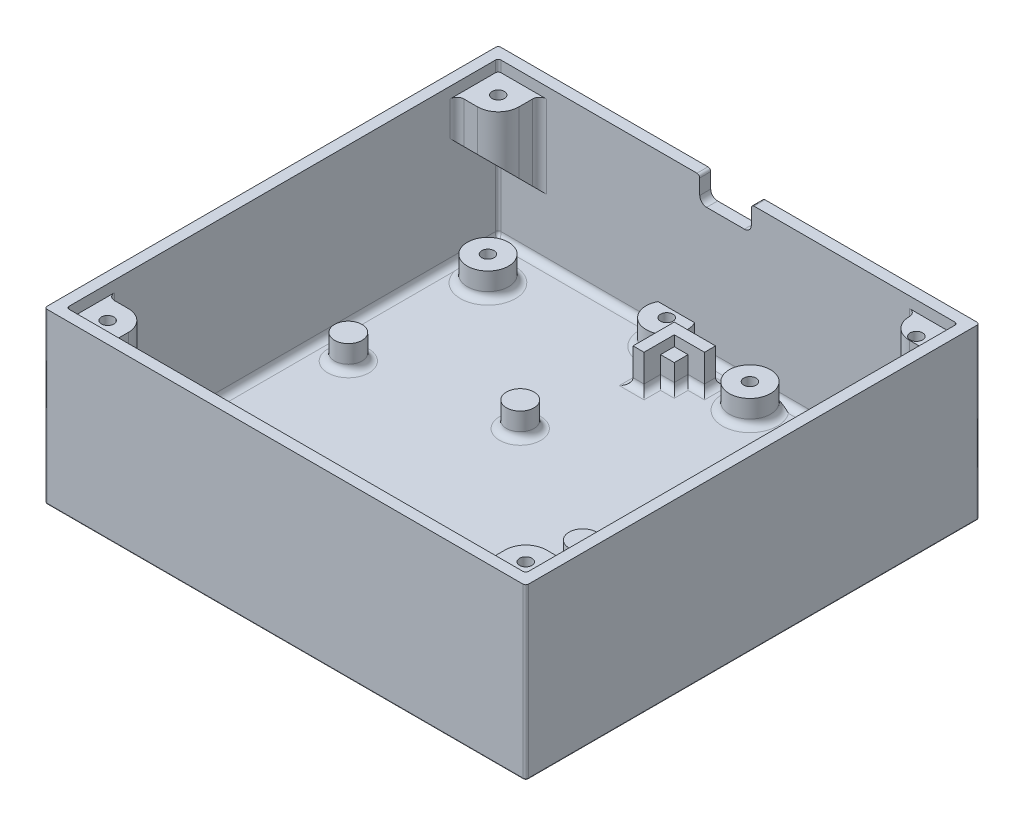
SolidWorks part; units mm, degrees
ref_plane "前视基准面" through (0, 0, 0) normal (0, 0, 1) x (1, 0, 0)
ref_plane "上视基准面" through (0, 0, 0) normal (0, 1, 0) x (1, 0, 0)
ref_plane "右视基准面" through (0, 0, 0) normal (1, 0, 0) x (0, 0, -1)
other "Configuration Table"
sketch "草图1" plane through (0, 0, 0) normal (0, 1, 0) x (1, 0, 0)
  line L1 (0, 0) -> (70, 0)
  line L2 (0, 0) -> (0, 66)
  line L3 (0, 66) -> (70, 66)
  line L4 (70, 0) -> (70, 66)
  dimension "D1" = 70
  dimension "D2" = 66
extrude "凸台-拉伸1" add sketch "草图1" along normal blind 2
sketch "草图2" plane through (0, 2, 0) normal (0, 1, 0) x (1, 0, 0)
  line L0 (70, 0) -> (70, 66) construction
  line L1 (66.8, 60) -> (31.6, 60)
  line L2 (66.8, 60) -> (66.8, 6)
  line L3 (66.8, 6) -> (31.6, 6)
  line L4 (31.6, 60) -> (31.6, 6)
  line L5 (70, 66) -> (0, 66) construction
  line L11 (68.4, 61.6) -> (30, 61.6)
  line L12 (30, 61.6) -> (30, 4.4)
  line L13 (68.4, 4.4) -> (30, 4.4)
  line L14 (68.4, 61.6) -> (68.4, 4.4)
  dimension "D1" = 35.2
  dimension "D2" = 54
  dimension "D3" = 3.2
  dimension "D4" = 6
  dimension "D5" = 1.6
extrude "凸台-拉伸2" add sketch "草图2" along normal blind 5
sketch "草图3" plane through (0, 2, 0) normal (0, 1, 0) x (1, 0, 0)
  line L0 (31.6, 6) -> (66.8, 6) construction
  line L1 (31.6, 60) -> (33.6, 60)
  line L2 (31.6, 60) -> (31.6, 58)
  line L3 (31.6, 58) -> (33.6, 58)
  line L4 (33.6, 60) -> (33.6, 58)
  line L5 (66.8, 60) -> (64.8, 60)
  line L6 (66.8, 60) -> (66.8, 58)
  line L7 (66.8, 58) -> (64.8, 58)
  line L8 (64.8, 60) -> (64.8, 58)
  line L9 (31.6, 6) -> (33.6, 6)
  line L10 (31.6, 6) -> (31.6, 8)
  line L11 (31.6, 8) -> (33.6, 8)
  line L12 (33.6, 6) -> (33.6, 8)
  line L13 (66.8, 6) -> (64.8, 6)
  line L14 (66.8, 6) -> (66.8, 8)
  line L15 (66.8, 8) -> (64.8, 8)
  line L16 (64.8, 6) -> (64.8, 8)
  line L17 (66.8, 6) -> (66.8, 60) construction
  circle A0 centre (49.3, 29) radius 2
  dimension "D9" = 4
  dimension "D11" = 17.5
  dimension "D1" = 2
  dimension "D2" = 2
  dimension "D3" = 2
  dimension "D4" = 2
  dimension "D5" = 2
  dimension "D6" = 2
  dimension "D7" = 2
  dimension "D8" = 2
  dimension "D10" = 23
extrude "凸台-拉伸3" add sketch "草图3" along normal blind 3.5
sketch "草图4" plane through (0, 7, 0) normal (0, 1, 0) x (1, 0, 0)
  line L0 (68.4, 61.6) -> (30, 61.6) construction
  line L1 (36, 61.6) -> (62.4, 61.6)
  line L2 (36, 61.6) -> (36, 60)
  line L3 (36, 60) -> (62.4, 60)
  line L4 (62.4, 61.6) -> (62.4, 60)
  line L5 (64.8, 60) -> (33.6, 60) construction
  line L6 (30, 61.6) -> (30, 4.4) construction
  line L7 (30, 55.6) -> (31.6, 55.6)
  line L8 (30, 55.6) -> (30, 10.4)
  line L9 (30, 10.4) -> (31.6, 10.4)
  line L10 (31.6, 55.6) -> (31.6, 10.4)
  line L11 (31.6, 58) -> (31.6, 8) construction
  line L12 (31.6, 6) -> (66.8, 6) construction
  line L13 (36, 6) -> (62.4, 6)
  line L14 (36, 6) -> (36, 4.4)
  line L15 (36, 4.4) -> (62.4, 4.4)
  line L16 (62.4, 6) -> (62.4, 4.4)
  line L17 (30, 4.4) -> (68.4, 4.4) construction
  line L18 (30, 61.6) -> (30, 4.4) construction
  line L19 (68.4, 4.4) -> (68.4, 61.6) construction
  line L20 (66.8, 6) -> (66.8, 60) construction
  line L21 (66.8, 55.6) -> (68.4, 55.6)
  line L22 (66.8, 55.6) -> (66.8, 10.4)
  line L23 (66.8, 10.4) -> (68.4, 10.4)
  line L24 (68.4, 55.6) -> (68.4, 10.4)
  line L25 (68.4, 61.6) -> (30, 61.6) construction
  dimension "D1" = 6
  dimension "D2" = 6
  dimension "D3" = 6
  dimension "D4" = 6
  dimension "D5" = 6
  dimension "D6" = 6
  dimension "D7" = 6
  dimension "D8" = 6
extrude "切除-拉伸1" cut sketch "草图4" against normal up to surface (5 mm away) up to face at (35, 2, -33)
sketch "草图7" plane through (0, 2, 0) normal (0, 1, 0) x (1, 0, 0)
  line L2 (30, 10.4) -> (30, 4.4) construction
  circle A3 centre (4, 5.4) radius 2
  dimension "D7" = 4
  dimension "D9" = 26
extrude "凸台-拉伸5" add sketch "草图7" along normal blind 5
sketch "草图8" plane through (0, 2, 0) normal (0, 1, 0) x (1, 0, 0)
  line L0 (70, 66) -> (0, 66) construction
  line L1 (30, 10.4) -> (30, 4.4) construction
  line L2 (30, 61.6) -> (30, 55.6) construction
  line L3 (30, 4.4) -> (36, 4.4) construction
  line L4 (36, 61.6) -> (30, 61.6) construction
  line L5 (68.4, 4.4) -> (68.4, 10.4) construction
  line L6 (62.4, 6) -> (66.8, 6) construction
  line L8 (31.6, 60) -> (31.6, 55.6) construction
  line L9 (36, 60) -> (31.6, 60) construction
  circle A0 centre (27.5, 63) radius 3
  circle A1 centre (6.5, 58) radius 3
  circle A3 centre (5, 10.3326) radius 2
  circle A4 centre (4, 5.4) radius 2 construction
  circle A5 centre (24, 7) radius 3
  circle A6 centre (6.2, 38) radius 2
  circle A7 centre (27.2, 42) radius 2
  circle A8 centre (49.4, 5) radius 3
  circle A9 centre (41.6, 61) radius 3
  dimension "D1" = 6
  dimension "D3" = 2.5
  dimension "D4" = 6
  dimension "D7" = 4
  dimension "D8" = 4.9326
  dimension "D9" = 1
  dimension "D10" = 6
  dimension "D11" = 6
  dimension "D12" = 2.6
  dimension "D13" = 4
  dimension "D14" = 4
  dimension "D15" = 28
  dimension "D16" = 24
  dimension "D5" = 23.5
  dimension "D6" = 3.6
  dimension "D17" = 6
  dimension "D18" = 19
  dimension "D19" = 1
  dimension "D20" = 6
  dimension "D21" = 10
  dimension "D22" = 1
  dimension "D2" = 3
extrude "凸台-拉伸9" add sketch "草图8" along normal blind 3.6
sketch "草图9" plane through (0, 2, 0) normal (0, 1, 0) x (1, 0, 0)
  line L0 (1.6, 64.4) -> (1.6, 1.6)
  line L1 (0, 66) -> (70, 66)
  line L2 (0, 66) -> (0, 0)
  line L3 (0, 0) -> (70, 0)
  line L4 (70, 66) -> (70, 0)
  line L5 (1.6, 1.6) -> (68.4, 1.6)
  line L6 (68.4, 64.4) -> (68.4, 1.6)
  line L7 (1.6, 64.4) -> (68.4, 64.4)
  line L8 (70, 0) -> (70, 66) construction
  line L9 (0, 0) -> (70, 0) construction
  dimension "D2" = 0
  dimension "D3" = 0
  dimension "D1" = 1.6
extrude "凸台-拉伸13" add sketch "草图9" along normal blind 21
sketch "草图10" plane through (0, 5.6, 0) normal (0, 1, 0) x (1, 0, 0)
  circle A0 centre (6.5, 58) radius 0.9
  circle A1 centre (27.5, 63) radius 0.9
  circle A2 centre (24, 7) radius 0.9
  circle A3 centre (41.6, 61) radius 0.9
  circle A4 centre (49.4, 5) radius 0.9
  dimension "D1" = 1.8
  dimension "D2" = 1.8
  dimension "D3" = 1.8
  dimension "D4" = 1.8
  dimension "D5" = 1.8
extrude "切除-拉伸2" cut sketch "草图10" against normal blind 5
sketch "草图11" plane through (0, 23, 0) normal (0, 1, 0) x (1, 0, 0)
  line L0 (68.4, 64.4) -> (30.1533, 64.4) construction
  line L1 (68.4, 64.4) -> (62.4, 64.4)
  line L2 (68.4, 64.4) -> (68.4, 60.4)
  line L3 (68.4, 60.4) -> (62.4, 60.4)
  line L4 (62.4, 64.4) -> (62.4, 60.4)
  line L5 (68.4, 61.6) -> (68.4, 64.4) construction
  line L7 (68.4, 1.6) -> (62.4, 1.6)
  line L8 (68.4, 1.6) -> (68.4, 7.6)
  line L9 (68.4, 7.6) -> (62.4, 7.6)
  line L10 (62.4, 1.6) -> (62.4, 7.6)
  line L11 (1.6, 1.6) -> (7.6, 1.6)
  line L12 (1.6, 1.6) -> (1.6, 7.6)
  line L13 (1.6, 7.6) -> (7.6, 7.6)
  line L14 (7.6, 1.6) -> (7.6, 7.6)
  line L15 (1.6, 64.4) -> (7.6, 64.4)
  line L16 (1.6, 64.4) -> (1.6, 58.4)
  line L17 (1.6, 58.4) -> (7.6, 58.4)
  line L18 (7.6, 64.4) -> (7.6, 58.4)
  dimension "D1" = 4
  dimension "D2" = 6
  dimension "D3" = 6
  dimension "D4" = 6
  dimension "D5" = 6
  dimension "D6" = 6
  dimension "D7" = 6
  dimension "D8" = 6
extrude "凸台-拉伸14" add sketch "草图11" against normal blind 6
chamfer "倒角1" distance 6 angle 45 4 edges at (65.4, 17, -64.4) (4.6, 17, -64.4) (65.4, 17, -1.6) (4.6, 17, -1.6)
sketch "草图12" plane through (0, 23, 0) normal (0, 1, 0) x (1, 0, 0)
  line L0 (1.6, 64.4) -> (1.6, 1.6)
  line L1 (0, 66) -> (70, 66)
  line L2 (0, 66) -> (0, 0)
  line L3 (0, 0) -> (70, 0)
  line L4 (70, 66) -> (70, 0)
  line L5 (1.6, 1.6) -> (68.4, 1.6)
  line L6 (68.4, 64.4) -> (68.4, 1.6)
  line L7 (1.6, 64.4) -> (68.4, 64.4)
  dimension "D1" = 1.6
extrude "凸台-拉伸15" add sketch "草图12" along normal blind 1.6
sketch "草图13" plane through (0, 23, 0) normal (0, 1, 0) x (1, 0, 0)
  line L0 (1.6, 58.4) -> (7.6, 58.4) construction
  line L1 (7.6, 58.4) -> (7.6, 64.4) construction
  circle A0 centre (4.6, 61.4) radius 0.9
  circle A1 centre (65.4, 61.4) radius 0.9
  circle A2 centre (65.4, 4.6) radius 0.9
  circle A3 centre (4.6, 4.6) radius 0.9
  dimension "D1" = 1.8
  dimension "D2" = 3
  dimension "D3" = 3
  dimension "D4" = 2
  dimension "D5" = 2
extrude "切除-拉伸3" cut sketch "草图13" against normal blind 6
sketch "草图14" plane through (0, 0, -64.4) normal (0, 0, 1) x (1, 0, 0)
  line L1 (30.9, 24.6) -> (38.4, 24.6)
  line L2 (30.9, 24.6) -> (30.9, 21)
  line L3 (30.9, 21) -> (38.4, 21)
  line L4 (38.4, 24.6) -> (38.4, 21)
  line L5 (68.4, 24.6) -> (1.6, 24.6) construction
  dimension "D1" = 3.6
  dimension "D2" = 7.5
  dimension "D3" = 0
  dimension "D4" = 30
extrude "切除-拉伸4" cut sketch "草图14" against normal blind 6
fillet "圆角1" radius 1 48 edges at (33.6, 2, -7) (32.6, 2, -8) (31.6, 2, -9.2) (30.8, 2, -10.4) (30, 2, -7.4) (33, 2, -4.4) (36, 2, -5.2) (34.8, 2, -6) (4, 2, -7.4) (6.5, 2, -61) (5, 2, -12.3326) (24, 2, -10) (49.4, 2, -8) (41.6, 2, -64) (49.3, 2, -31) (27.2, 2, -44) (6.2, 2, -40) (65.4, 2, -4.4) (62.4, 2, -5.2) (63.6, 2, -6) (64.8, 2, -7) (65.8, 2, -8) (66.8, 2, -9.2) (67.6, 2, -10.4) (65.4, 2, -61.6) (67.6, 2, -55.6) (66.8, 2, -56.8) (65.8, 2, -58) (64.8, 2, -59) (63.6, 2, -60) (62.4, 2, -60.8) (30.5, 2, -63) (33.0766, 2, -61.6) (36, 2, -60.8) (33.6, 2, -59) (31.6, 2, -56.8) (32.6, 2, -58) (34.8, 2, -60) (30.8, 2, -55.6) (30, 2, -58.4708) (25.9689, 2, -60.4201) (49.2766, 2, -64.4) (68.4, 2, -63) (68.4, 2, -33) (68.4, 2, -3) (35, 2, -1.6) (1.6, 2, -33) (13.2234, 2, -64.4)
fillet "圆角2" radius 1 2 edges at (38.4, 21, -65.2) (30.9, 21, -65.2)
fillet "圆角3" radius 3 4 edges at (7.6, 20, -7.6) (62.4, 20, -7.6) (62.4, 19, -60.4) (7.6, 20, -58.4)
fillet "圆角4" radius 1 8 edges at (1.6, 20, -7.6) (7.6, 17, -1.6) (62.4, 17, -1.6) (68.4, 20, -7.6) (68.4, 19, -60.4) (62.4, 17, -64.4) (1.6, 20, -58.4) (7.6, 17, -64.4)
fillet "圆角5" radius 0.4 18 edges at (68.1071, 2.2929, -64.1071) (1.8929, 2.2929, -64.1071) (1.8929, 2.2929, -1.8929) (68.1071, 2.2929, -1.8929) (68.4, 23.8, -1.6) (68.4, 7, -64.4) (68.4, 23.8, -64.4) (1.6, 23.8, -64.4) (1.6, 7, -64.4) (1.6, 23.8, -1.6) (1.6, 7, -1.6) (68.4, 7, -1.6) (0, 12.3, 0) (70, 12.3, 0) (70, 12.3, -66) (0, 12.3, -66) (30.9, 24.6, -65.2) (38.4, 24.6, -65.2)
fillet "圆角6" radius 0.2 8 edges at (69.8828, 0, -0.1172) (70, 0, -33) (69.8828, 0, -65.8828) (35, 0, -66) (0.1172, 0, -65.8828) (0, 0, -33) (0.1172, 0, -0.1172) (35, 0, 0)
